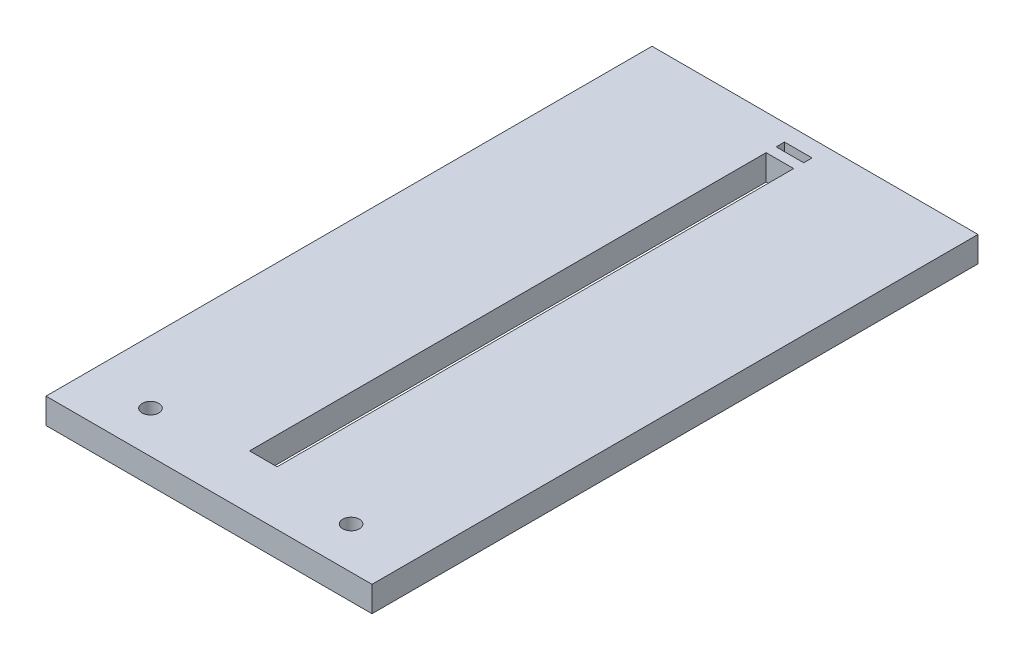
SolidWorks part; units mm, degrees
ref_plane "Front Plane" through (0, 0, 0) normal (0, 0, 1) x (1, 0, 0)
ref_plane "Top Plane" through (0, 0, 0) normal (0, 1, 0) x (1, 0, 0)
ref_plane "Right Plane" through (0, 0, 0) normal (1, 0, 0) x (0, 0, -1)
sketch "Sketch1" plane through (0, 0, 0) normal (0, 1, 0) x (1, 0, 0)
  line L1 (-19.5, 0) -> (19.5, 0)
  line L2 (-19.5, 0) -> (-19.5, 72.5)
  line L3 (-19.5, 72.5) -> (19.5, 72.5)
  line L4 (19.5, 0) -> (19.5, 72.5)
  point P5 (0, 0)
  dimension "D1" = 39
  dimension "D2" = 72.5
extrude "Boss-Extrude1" add sketch "Sketch1" along normal blind 3.05 contours L2 | L1 L4 L3 L2 | L4 region at (0, 0, -36.25)
sketch "Sketch4" plane through (0, 3.05, 0) normal (0, 1, 0) x (1, 0, 0)
  line L0 (-19.5, 72.5) -> (19.5, 72.5) construction
  line L2 (-19.5, 0) -> (19.5, 0) construction
  line L3 (1.65, 70.5) -> (-1.65, 70.5)
  line L4 (-1.65, 70.5) -> (-1.65, 69.5)
  line L5 (-1.65, 69.5) -> (1.65, 69.5)
  line L6 (1.65, 69.5) -> (1.65, 70.5)
  line L7 (0, 0) -> (0, 72.5) construction
  line L9 (1.65, 68.3) -> (-1.65, 68.3)
  line L10 (-1.65, 68.3) -> (-1.65, 6.5)
  line L11 (-1.65, 6.5) -> (1.65, 6.5)
  line L12 (1.65, 6.5) -> (1.65, 68.3)
  point P6 (0, 6.5)
  point P10 (0, 70.5)
  point P22 (0, 68.3)
  dimension "D1" = 2
  dimension "D2" = 1
  dimension "D3" = 1.2
  dimension "D4" = 3.3
  dimension "D7" = 6.5
extrude "Cut-Extrude1" cut sketch "Sketch4" against normal through all contours L5 L7 L3 L4 | L11 L7 L9 L10 | L7 L11 L12 L9 | L7 L5 L6 L3 | L6 L3 L4 L5 region at (0.825, 3.05, -70) region at (0.825, 3.05, -37.4) region at (-0.825, 3.05, -37.4) region at (-0.825, 3.05, -70)
sketch "Sketch7" plane through (0, 3.05, 0) normal (0, 1, 0) x (1, 0, 0)
  line L0 (0, 0) -> (-12, 0)
  line L1 (-19.5, 0) -> (19.5, 0) construction
  line L2 (-12, 0) -> (-12, 5)
  line L4 (0, 0) -> (0, 70) construction
  circle A0 centre (-12, 5) radius 1
  circle A2 centre (12, 5) radius 1
  dimension "D3" = 2
  dimension "D1" = 12
  dimension "D2" = 5
extrude "Cut-Extrude4" cut sketch "Sketch7" against normal through all contours A0 L2 | L2 A0 | A2 region at (-11.3129, 3.05, -4.3129)
